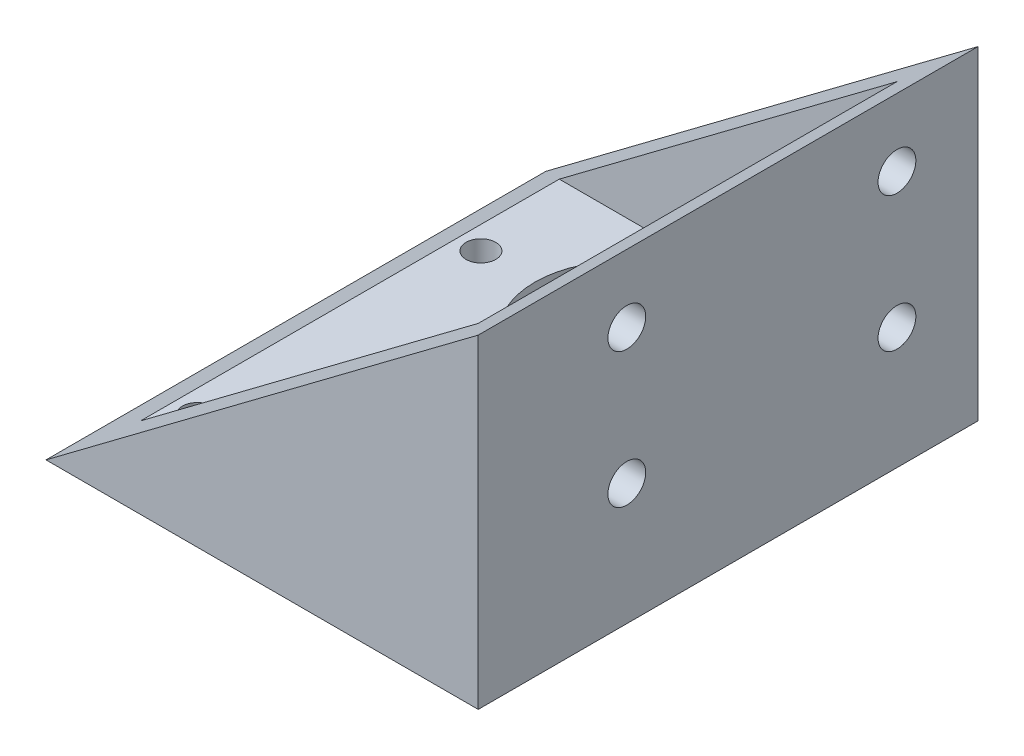
SolidWorks part; units mm, degrees
ref_plane "正面" through (0, 0, 0) normal (0, 0, 1) x (1, 0, 0)
ref_plane "平面" through (0, 0, 0) normal (0, 1, 0) x (1, 0, 0)
ref_plane "右側面" through (0, 0, 0) normal (1, 0, 0) x (0, 0, -1)
sketch "ｽｹｯﾁ1" plane through (0, 0, 0) normal (0, 0, 1) x (1, 0, 0)
  line L0 (0, 0) -> (32, 0)
  line L1 (32, 0) -> (32, 24)
  line L2 (32, 24) -> (0, 0)
  dimension "D1" = 32
  dimension "D2" = 24
extrude "ﾎﾞｽ - 押し出し1" add sketch "ｽｹｯﾁ1" along normal blind 37
shell "ｼｪﾙ1" thickness 3 removed face at (16, 12, 18.5)
sketch "ｽｹｯﾁ2" plane through (0, 0, 0) normal (0, -1, 0) x (1, 0, 0)
  line L1 (26.7, 31.5) -> (5.7, 31.5) construction
  line L2 (26.7, 31.5) -> (26.7, 10.5) construction
  line L3 (26.7, 10.5) -> (5.7, 10.5) construction
  line L4 (5.7, 31.5) -> (5.7, 10.5) construction
  line L5 (26.7, 31.5) -> (5.7, 10.5) construction
  line L6 (26.7, 10.5) -> (5.7, 31.5) construction
  line L7 (29, 34) -> (29, 3) construction
  line L8 (32, 37) -> (0, 37) construction
  circle A0 centre (26.7, 10.5) radius 1.1
  circle A1 centre (5.7, 10.5) radius 1.1
  circle A2 centre (5.7, 31.5) radius 1.1
  circle A3 centre (26.7, 31.5) radius 1.1
  point P0 (16.2, 21)
  dimension "D1" = 2.2
  dimension "D2" = 21
  dimension "D3" = 21
  dimension "D4" = 2.3
  dimension "D5" = 5.5
extrude "ｶｯﾄ - 押し出し1" cut sketch "ｽｹｯﾁ2" against normal blind 30
sketch "ｽｹｯﾁ3" plane through (0, 0, 0) normal (0, -1, 0) x (1, 0, 0)
  circle A0 centre (16.2, 10.5) radius 6.5
  circle A2 centre (26.7, 31.5) radius 1.1
  circle A3 centre (26.7, 31.5) radius 1.1
  circle A4 centre (5.7, 31.5) radius 1.1
  circle A5 centre (5.7, 31.5) radius 1.1
  circle A6 centre (5.7, 10.5) radius 1.1
  circle A7 centre (5.7, 10.5) radius 1.1
  circle A8 centre (26.7, 10.5) radius 1.1
  circle A9 centre (26.7, 10.5) radius 1.1
  dimension "D5" = 13
  dimension "D6" = 10.5
  dimension "D1" = 0
  dimension "D2" = 0
  dimension "D3" = 0
  dimension "D4" = 0
extrude "ｶｯﾄ - 押し出し2" cut sketch "ｽｹｯﾁ3" against normal blind 5 contours A0
sketch "ｽｹｯﾁ4" plane through (32, 0, 0) normal (1, 0, 0) x (0, 0, -1)
  line L0 (-37, 24) -> (0, 24) construction
  line L1 (-6, 19) -> (-26, 19) construction
  line L2 (-6, 19) -> (-6, 9) construction
  line L3 (-6, 9) -> (-26, 9) construction
  line L4 (-26, 19) -> (-26, 9) construction
  line L5 (-6, 19) -> (-26, 9) construction
  line L6 (-6, 9) -> (-26, 19) construction
  circle A0 centre (-6, 19) radius 1.4
  circle A1 centre (-26, 19) radius 1.4
  circle A2 centre (-26, 9) radius 1.4
  circle A3 centre (-6, 9) radius 1.4
  point P0 (-16, 14)
  dimension "D1" = 2.8
  dimension "D2" = 20
  dimension "D3" = 10
  dimension "D4" = 10
  dimension "D5" = 3
extrude "ｶｯﾄ - 押し出し3" cut sketch "ｽｹｯﾁ4" against normal blind 5
equation "\"D6@ｽｹｯﾁ3\"=21/2"
